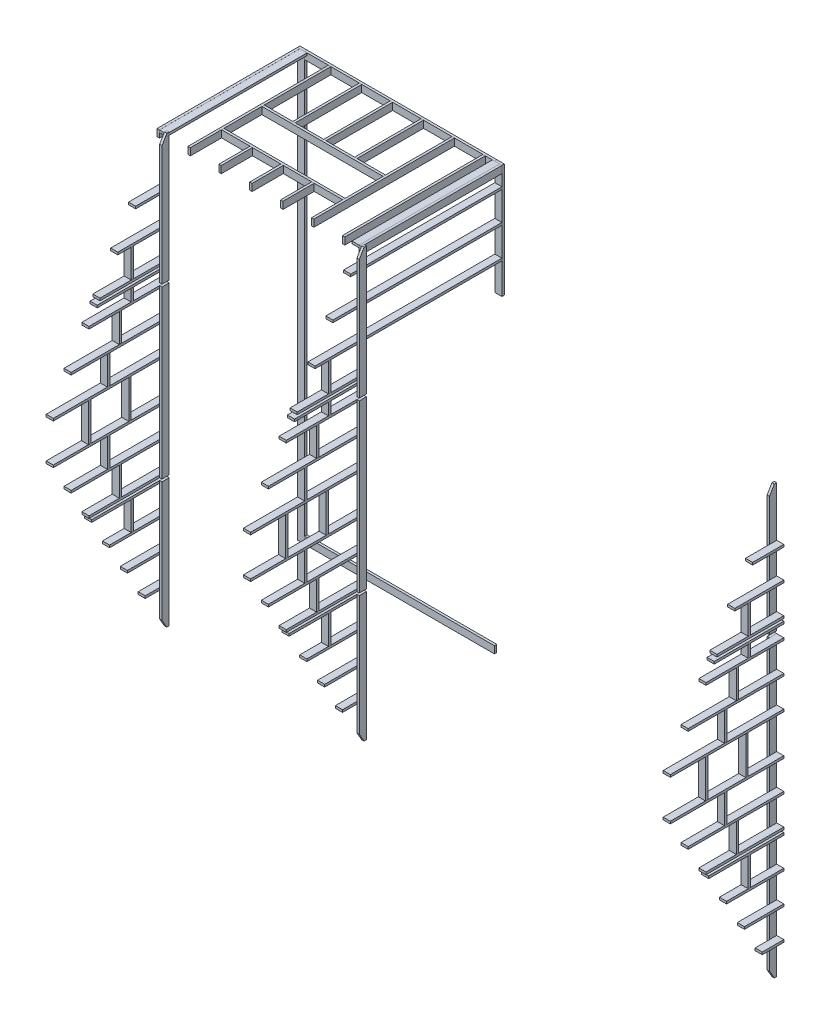
SolidWorks part; units mm, degrees
ref_plane "Спереди" through (0, 0, 0) normal (0, 0, 1) x (1, 0, 0)
ref_plane "Сверху" through (0, 0, 0) normal (0, 1, 0) x (1, 0, 0)
ref_plane "Справа" through (0, 0, 0) normal (1, 0, 0) x (0, 0, -1)
other "Configuration Table"
sketch "Эскиз2" plane through (-110, 0, 0) normal (-1, 0, 0) x (0, 0, 1)
  line L0 (-50, 0) -> (-50, 6600) construction
  line L1 (-50, 2700) -> (1529.9782, 2700)
  line L2 (-50, 2700) -> (-50, 2650)
  line L3 (-50, 2650) -> (1529.9782, 2650)
  line L4 (1529.9782, 2700) -> (1529.9782, 2650)
  line L5 (-50, 4100) -> (2338.2686, 4100)
  line L6 (-50, 4100) -> (-50, 4050)
  line L7 (-50, 4050) -> (2338.2686, 4050)
  line L8 (2338.2686, 4100) -> (2338.2686, 4050)
  line L9 (2651.9993, 4500) -> (-50, 4500) construction
  line L10 (-50, 8900) -> (-50, 100) construction
  line L11 (0, 0) -> (2598.0762, 4500) construction
  line L12 (2651.9993, 4500) -> (53.923, 0) construction
  line L13 (0, 9000) -> (2598.0762, 4500) construction
  line L14 (1550, 4100) -> (750, 4100) construction
  line L15 (-50, 4900) -> (-50, 4950)
  line L16 (-50, 4900) -> (2338.2686, 4900)
  line L17 (2338.2686, 4900) -> (2338.2686, 4950)
  line L18 (-50, 4950) -> (2338.2686, 4950)
  line L19 (1550, 4100) -> (1550, 4900) construction
  line L28 (1550, 4899) -> (1600, 4899)
  line L29 (1550, 4899) -> (1550, 4101)
  line L30 (1550, 4101) -> (1600, 4101)
  line L31 (1600, 4899) -> (1600, 4101)
  line L32 (750, 4100) -> (750, 4900) construction
  line L33 (750, 4899) -> (700, 4899)
  line L34 (750, 4899) -> (750, 4101)
  line L35 (750, 4101) -> (700, 4101)
  line L36 (700, 4899) -> (700, 4101)
  line L38 (1962.9909, 3400) -> (-50, 3400)
  line L39 (1962.9909, 3400) -> (1962.9909, 3450)
  line L40 (1962.9909, 3450) -> (-50, 3450)
  line L41 (-50, 3400) -> (-50, 3450)
  line L43 (-50, 2800) -> (1587.7132, 2800)
  line L44 (-50, 2800) -> (-50, 2750)
  line L45 (-50, 2750) -> (1587.7132, 2750)
  line L46 (1587.7132, 2800) -> (1587.7132, 2750)
  line L47 (1154.7005, 2000) -> (-50, 2000)
  line L48 (1154.7005, 2000) -> (1154.7005, 2050)
  line L49 (1154.7005, 2050) -> (-50, 2050)
  line L50 (-50, 2000) -> (-50, 2050)
  line L51 (779.4229, 1350) -> (-50, 1350)
  line L52 (779.4229, 1350) -> (779.4229, 1400)
  line L53 (779.4229, 1400) -> (-50, 1400)
  line L54 (-50, 1350) -> (-50, 1400)
  line L55 (404.1452, 700) -> (-50, 700)
  line L56 (404.1452, 700) -> (404.1452, 750)
  line L57 (404.1452, 750) -> (-50, 750)
  line L58 (-50, 700) -> (-50, 750)
  line L59 (1200, 4049) -> (1150, 4049)
  line L60 (1200, 4049) -> (1200, 3451)
  line L61 (1200, 3451) -> (1150, 3451)
  line L62 (1150, 4049) -> (1150, 3451)
  line L63 (950, 3399) -> (900, 3399)
  line L64 (950, 3399) -> (950, 2801)
  line L65 (950, 2801) -> (900, 2801)
  line L66 (900, 3399) -> (900, 2801)
  line L67 (700, 2649) -> (650, 2649)
  line L68 (700, 2649) -> (700, 2051)
  line L69 (700, 2051) -> (650, 2051)
  line L70 (650, 2649) -> (650, 2051)
  line L71 (1200, 4951) -> (1150, 4951)
  line L80 (900, 5601) -> (900, 6199)
  line L81 (950, 6199) -> (900, 6199)
  line L82 (950, 5601) -> (950, 6199)
  line L83 (950, 5601) -> (900, 5601)
  line L84 (1150, 4951) -> (1150, 5549)
  line L85 (1200, 5549) -> (1150, 5549)
  line L86 (1200, 4951) -> (1200, 5549)
  line L95 (1587.7132, 6200) -> (1587.7132, 6250)
  line L96 (-50, 6250) -> (1587.7132, 6250)
  line L97 (-50, 6200) -> (-50, 6250)
  line L98 (-50, 6200) -> (1587.7132, 6200)
  line L99 (-50, 5600) -> (-50, 5550)
  line L100 (1962.9909, 5550) -> (-50, 5550)
  line L101 (1962.9909, 5600) -> (1962.9909, 5550)
  line L102 (1962.9909, 5600) -> (-50, 5600)
  line L107 (-50, 4500) -> (-50, 9000) construction
  line L108 (-50, 9000) -> (0, 9000) construction
  line L110 (-50, 6550) -> (1414.5082, 6550)
  line L111 (-50, 6550) -> (-50, 6500)
  line L112 (-50, 6500) -> (1414.5082, 6500)
  line L113 (1414.5082, 6550) -> (1414.5082, 6500)
  line L114 (-50, 6600) -> (1356.7731, 6600)
  line L115 (-50, 6600) -> (-50, 6650)
  line L116 (-50, 6650) -> (1356.7731, 6650)
  line L117 (1356.7731, 6600) -> (1356.7731, 6650)
  line L118 (-50, 7300) -> (981.4955, 7300)
  line L119 (-50, 7300) -> (-50, 7250)
  line L120 (-50, 7250) -> (981.4955, 7250)
  line L121 (981.4955, 7300) -> (981.4955, 7250)
  line L122 (650, 6499) -> (700, 6499)
  line L123 (650, 6499) -> (650, 6251)
  line L124 (650, 6251) -> (700, 6251)
  line L125 (700, 6499) -> (700, 6251)
  line L126 (650, 7249) -> (700, 7249)
  line L127 (650, 7249) -> (650, 6651)
  line L128 (650, 6651) -> (700, 6651)
  line L129 (700, 7249) -> (700, 6651)
  line L130 (-50, 7950) -> (606.2178, 7950)
  line L131 (-50, 7950) -> (-50, 7900)
  line L132 (-50, 7900) -> (606.2178, 7900)
  line L133 (606.2178, 7950) -> (606.2178, 7900)
  dimension "D1" = 50
  dimension "D2" = 800
  dimension "D3" = 1
  dimension "D4" = 1
  dimension "D5" = 600
  dimension "D6" = 600
  dimension "D7" = 600
  dimension "D8" = 600
  dimension "D9" = 600
  dimension "D10" = 1
  dimension "D11" = 1
  dimension "D12" = 400
  dimension "D13" = 1
  dimension "D14" = 1
  dimension "D15" = 200
  dimension "D16" = 200
  dimension "D17" = 1
  dimension "D18" = 1
  dimension "D19" = 200
  dimension "D20" = 600
  dimension "D21" = 1
  dimension "D22" = 1
  dimension "D23" = 600
ref_plane "Плоскость1" through (-8990, 0, 0) normal (1, 0, 0) x (0, 0, -1)
ref_plane "Плоскость2" through (-13140, 0, 0) normal (1, 0, 0) x (0, 0, -1)
extrude "Бобышка-Вытянуть1" add sketch "Эскиз2" along normal blind 50 and the other way blind 100
extrude "Бобышка-Вытянуть2" add sketch "Эскиз2<2>" against normal blind 150 from surface separate body starting at plane "Плоскость1"
sketch "Эскиз2<2>" plane through (-110, 0, 0) normal (-1, 0, 0) x (0, 0, 1) same geometry as "Эскиз2"
extrude "Бобышка-Вытянуть3" add sketch "Эскиз2<3>" against normal blind 150 from surface separate body starting at plane "Плоскость2"
sketch "Эскиз2<3>" plane through (-110, 0, 0) normal (-1, 0, 0) x (0, 0, 1) same geometry as "Эскиз2"
sketch "Эскиз3" plane through (-160, 0, 0) normal (-1, 0, 0) x (0, 0, 1)
  line L0 (0, 0) -> (100, 173.2051)
  line L1 (-50, 2700) -> (100, 2700)
  line L2 (-50, 2700) -> (-50, 0)
  line L3 (-50, 0) -> (0, 0)
  line L4 (100, 2700) -> (100, 173.2051)
  line L5 (0, 0) -> (2598.0762, 4500) construction
  line L6 (-50, 6250) -> (1587.7132, 6250) construction
  line L7 (-50, 2750) -> (100, 2750)
  line L8 (-50, 2750) -> (-50, 6250)
  line L9 (-50, 6250) -> (100, 6250)
  line L10 (100, 2750) -> (100, 6250)
  line L12 (2598.0762, 4500) -> (-50, 4500) construction
  line L13 (-50, 6300) -> (100, 6300)
  line L14 (100, 6300) -> (100, 8826.7949)
  line L15 (0, 9000) -> (100, 8826.7949)
  line L16 (-50, 9000) -> (0, 9000)
  line L17 (-50, 6300) -> (-50, 9000)
  dimension "D1" = 150
extrude "Бобышка-Вытянуть4" add sketch "Эскиз3" along normal blind 50 separate body
extrude "Бобышка-Вытянуть5" add sketch "Эскиз3<2>" against normal blind 50 from surface separate body starting at face at (-8840, 6950, 675)
sketch "Эскиз3<2>" plane through (-160, 0, 0) normal (-1, 0, 0) x (0, 0, 1) same geometry as "Эскиз3"
extrude "Бобышка-Вытянуть6" add sketch "Эскиз3<3>" against normal blind 50 from surface separate body starting at face at (-12990, 7275, 465.7477)
sketch "Эскиз3<3>" plane through (-160, 0, 0) normal (-1, 0, 0) x (0, 0, 1) same geometry as "Эскиз3"
ref_plane "Плоскость3" through (0, 0, -3000) normal (0, 0, -1) x (-1, 0, 0)
sketch "Эскиз4" plane through (0, 0, -3000) normal (0, 0, -1) x (-1, 0, 0)
  line L1 (8840, 8990) -> (8990, 8990)
  line L2 (8840, 8990) -> (8840, 6600)
  line L3 (8840, 6600) -> (8990, 6600)
  line L4 (8990, 8990) -> (8990, 6600)
  line L5 (12990, 8990) -> (13140, 8990)
  line L6 (12990, 8990) -> (12990, 10)
  line L7 (12990, 10) -> (13140, 10)
  line L8 (13140, 8990) -> (13140, 10)
  line L9 (8991, 8990) -> (12989, 8990)
  line L10 (8991, 8990) -> (8991, 8840)
  line L11 (8991, 8840) -> (12989, 8840)
  line L12 (12989, 8990) -> (12989, 8840)
  line L13 (9000, 160) -> (12989, 160)
  line L14 (9000, 160) -> (9000, 10)
  line L15 (9000, 10) -> (12989, 10)
  line L16 (12989, 160) -> (12989, 10)
  line L17 (8990, 7950) -> (8990, 7900) construction
  line L18 (12990, 6300) -> (12990, 9000) construction
  line L20 (12940, 0) -> (12990, 0) construction
  line L21 (8840, 6300) -> (8840, 9000) construction
  line L22 (8790, 9000) -> (8840, 9000) construction
  line L23 (8840, 6600) -> (8990, 6600) construction
  line L24 (8990, 6650) -> (8990, 6600) construction
  line L26 (9000, 203) -> (9000, 1000) construction
  point P18 (0, 0)
  point P22 (12990, 72.7425)
  point P23 (12990, 0)
  point P25 (8990, 10)
  point P26 (9000, 85)
  point P27 (0, 0)
  point P28 (12990, 9.5294)
  point P31 (0, 0)
  point P32 (0, 0)
  point P33 (0, 0)
  point P34 (8840, 8980.0157)
  point P39 (8990, 6600)
  point P44 (8840, 160)
  point P45 (0, 0)
  point P47 (0, 0)
  dimension "D1" = 1
  dimension "D2" = 150
  dimension "D3" = 1
  dimension "D4" = 1
  dimension "D5" = 10
  dimension "D6" = 10
extrude "Бобышка-Вытянуть7" add sketch "Эскиз4" against normal blind 50 separate body
sketch "Эскиз5" plane through (-8990, 0, 0) normal (-1, 0, 0) x (0, 0, 1)
  line L0 (-2950, 6600) -> (-2950, 8990) construction
  line L1 (-50, 7300) -> (-2950, 7300)
  line L2 (-50, 7300) -> (-50, 7250)
  line L3 (-50, 7250) -> (-2950, 7250)
  line L4 (-2950, 7300) -> (-2950, 7250)
  line L5 (-50, 7900) -> (606.2178, 7900) construction
  line L6 (-50, 7950) -> (-2950, 7950)
  line L7 (-50, 7950) -> (-50, 7900)
  line L8 (-50, 7900) -> (-2950, 7900)
  line L9 (-2950, 7950) -> (-2950, 7900)
  line L10 (230.9401, 8600) -> (-2950, 8600)
  line L11 (230.9401, 8600) -> (230.9401, 8550)
  line L12 (230.9401, 8550) -> (-2950, 8550)
  line L13 (-2950, 8600) -> (-2950, 8550)
  line L14 (0, 9000) -> (2598.0762, 4500) construction
  point P16 (-50, 7250)
  point P18 (-50, 7900)
  point P21 (230.9401, 8600)
  dimension "D1" = 600
extrude "Бобышка-Вытянуть8" add sketch "Эскиз5" against normal up to vertex (150 mm away) separate body up to point (-8840, 7950, -50)
sketch "Эскиз6" plane through (-8840, 0, 0) normal (-1, 0, 0) x (0, 0, 1)
  line L0 (0, 9000) -> (2598.0762, 4500) construction
  line L1 (-2950, 8990) -> (5.7735, 8990)
  line L2 (-2950, 8990) -> (-2950, 8840)
  line L3 (-2950, 8840) -> (5.7735, 8840)
  line L4 (5.7735, 8990) -> (5.7735, 8840)
  point P5 (-28.0897, 8990)
  point P6 (0, 0)
  dimension "D1" = 150
extrude "Бобышка-Вытянуть9" add sketch "Эскиз6" along normal blind 50 separate body
sketch "Эскиз7" plane through (0, 0, -2950) normal (0, 0, 1) x (1, 0, 0)
  line L0 (-8991, 8840) -> (-12989, 8840) construction
  line L1 (-13140, 8990) -> (-13090, 8990)
  line L2 (-13140, 8990) -> (-13140, 8840)
  line L3 (-13140, 8840) -> (-13090, 8840)
  line L4 (-13090, 8990) -> (-13090, 8840)
  line L5 (-8890, 8990) -> (-8840, 8990) construction
  line L6 (-13140, 8990) -> (-12990, 8990) construction
  line L7 (-13089, 8990) -> (-12939, 8990)
  line L8 (-13089, 8990) -> (-13089, 8940)
  line L9 (-13089, 8940) -> (-12939, 8940)
  line L10 (-12939, 8990) -> (-12939, 8940)
  line L11 (-12989, 8990) -> (-8991, 8990) construction
  line L12 (-9040, 8990) -> (-8890, 8990)
  line L13 (-9040, 8990) -> (-9040, 8940)
  line L14 (-9040, 8940) -> (-8890, 8940)
  line L15 (-8890, 8990) -> (-8890, 8940)
  line L16 (-8890, 8840) -> (-8890, 8990) construction
  line L17 (-8890, 8840) -> (-8840, 8840) construction
  line L19 (-12490, 8990) -> (-12440, 8990)
  line L20 (-12490, 8990) -> (-12490, 8840)
  line L21 (-12490, 8840) -> (-12440, 8840)
  line L22 (-12440, 8990) -> (-12440, 8840)
  line L23 (-11840, 8990) -> (-11790, 8990)
  line L24 (-11840, 8990) -> (-11840, 8840)
  line L25 (-11840, 8840) -> (-11790, 8840)
  line L26 (-11790, 8990) -> (-11790, 8840)
  line L27 (-11190, 8990) -> (-11140, 8990)
  line L28 (-11190, 8990) -> (-11190, 8840)
  line L29 (-11190, 8840) -> (-11140, 8840)
  line L30 (-11140, 8990) -> (-11140, 8840)
  line L31 (-10540, 8990) -> (-10490, 8990)
  line L32 (-10540, 8990) -> (-10540, 8840)
  line L33 (-10540, 8840) -> (-10490, 8840)
  line L34 (-10490, 8990) -> (-10490, 8840)
  line L35 (-9890, 8990) -> (-9840, 8990)
  line L36 (-9890, 8990) -> (-9890, 8840)
  line L37 (-9890, 8840) -> (-9840, 8840)
  line L38 (-9840, 8990) -> (-9840, 8840)
  line L39 (-9240, 8990) -> (-9190, 8990)
  line L40 (-9240, 8990) -> (-9240, 8840)
  line L41 (-9240, 8840) -> (-9190, 8840)
  line L42 (-9190, 8990) -> (-9190, 8840)
  dimension "D1" = 1
  dimension "D2" = 600
  dimension "D3" = 600
  dimension "D4" = 600
  dimension "D5" = 600
  dimension "D6" = 600
  dimension "D7" = 600
  dimension "D8" = 300
extrude "Бобышка-Вытянуть10" add sketch "Эскиз7" along normal up to surface (2955.7735 mm away) separate body up to face at (-8865, 8915, 5.7735)
sketch "Эскиз8" plane through (0, 9000, 0) normal (0, 1, 0) x (1, 0, 0)
  line L2 (-9890, 650) -> (-12440, 650)
  line L3 (-9890, 650) -> (-9890, 1550)
  line L4 (-9890, 1550) -> (-12440, 1550)
  line L5 (-12440, 650) -> (-12440, 1550)
  line L7 (-9890, 700) -> (-12440, 700) construction
  line L8 (-12440, 1500) -> (-9890, 1500) construction
  line L9 (-12440, -5.7735) -> (-12440, 2950) construction
  line L10 (-9890, -5.7735) -> (-9890, 2950) construction
  point P6 (-9890, 650)
  point P8 (-12440, 1550)
  point P12 (-12440, 1550)
  point P14 (0, 0)
  dimension "D1" = 50
  dimension "D2" = 50
extrude "Вырез-Вытянуть1" cut sketch "Эскиз8" against normal blind 488
sketch "Эскиз9" plane through (0, 8840, 0) normal (0, -1, 0) x (1, 0, 0)
  line L0 (-12440, 5.7735) -> (-12440, -2950) construction
  line L1 (-12440, -650) -> (-9890, -650)
  line L2 (-12440, -650) -> (-12440, -700)
  line L3 (-12440, -700) -> (-9890, -700)
  line L4 (-9890, -650) -> (-9890, -700)
  line L7 (-12440, -1500) -> (-9890, -1500)
  line L8 (-12440, -1500) -> (-12440, -1550)
  line L9 (-12440, -1550) -> (-9890, -1550)
  line L10 (-9890, -1500) -> (-9890, -1550)
  line L11 (-11840, -650) -> (-11790, -650) construction
  line L12 (-9890, 5.7735) -> (-9890, -2950) construction
  line L13 (-11140, -1550) -> (-11190, -1550) construction
  line L14 (-9840, 5.7735) -> (-9890, 5.7735) construction
  point P6 (-9890, -700)
  point P7 (0, 0)
  point P12 (0, 0)
  point P17 (-9890, -1500)
  point P20 (0, 0)
  point P21 (0, 0)
  point P26 (0, 0)
extrude "Бобышка-Вытянуть11" add sketch "Эскиз9" against normal up to surface (150 mm away) separate body up to face at (-8915, 8990, -2975)
